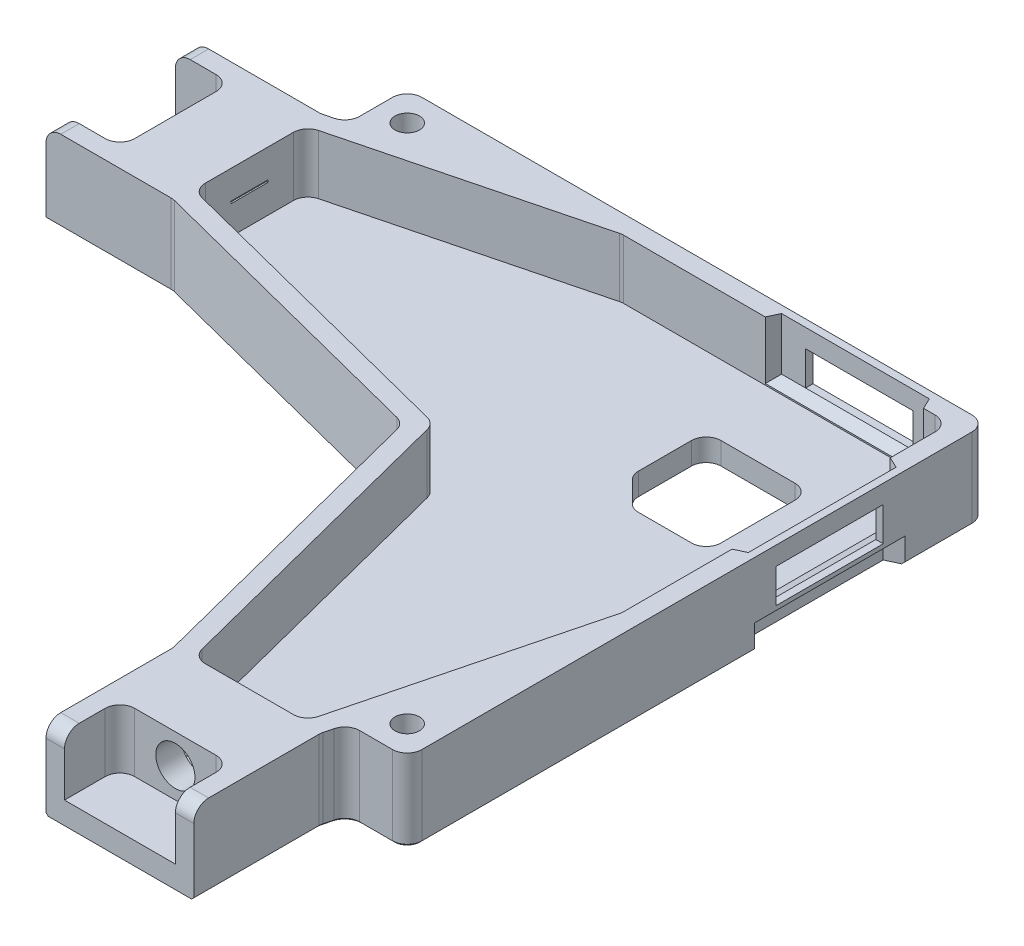
SolidWorks part; units mm, degrees
ref_plane "Front Plane" through (0, 0, 0) normal (0, 0, 1) x (1, 0, 0)
ref_plane "Top Plane" through (0, 0, 0) normal (0, 1, 0) x (1, 0, 0)
ref_plane "Right Plane" through (0, 0, 0) normal (1, 0, 0) x (0, 0, -1)
sketch "x Sensor" plane through (0, 0, 0) normal (0, 0, 1) x (1, 0, 0)
  line L0 (-13, 0) -> (0, 0) construction
  line L1 (-22.5, 1.5) -> (-13, 1.5)
  line L2 (-22.5, 1.5) -> (-22.5, -1.5)
  line L3 (-22.5, -1.5) -> (-13, -1.5)
  line L4 (-13, 1.5) -> (-13, -1.5)
  point P4 (-13, 0)
  dimension "D1" = 13
  dimension "D2" = 3
  dimension "D3" = 9.5
sketch "y Sensor" plane through (0, 0, 0) normal (1, 0, 0) x (0, 0, -1)
  line L0 (-13, 0) -> (0, 0) construction
  line L1 (-13, 1.5) -> (-22.5, 1.5)
  line L2 (-13, 1.5) -> (-13, -1.5)
  line L3 (-13, -1.5) -> (-22.5, -1.5)
  line L4 (-22.5, 1.5) -> (-22.5, -1.5)
  line L5 (0, 1.5) -> (0, -1.5) construction
  dimension "D1" = 9.5
  dimension "D2" = 13
ref_plane "y LED plane" through (-80, 0, 0) normal (1, 0, 0) x (0, 0, -1)
ref_plane "x LED plane" through (0, 0, 80) normal (0, 0, 1) x (1, 0, 0)
sketch "y LED" plane through (-80, 0, 0) normal (1, 0, 0) x (0, 0, -1)
  line L0 (-17.75, 1.5) -> (-17.75, -1.5) construction
  line L1 (-13, 1.5) -> (-22.5, 1.5) construction
  line L2 (-13, -1.5) -> (-22.5, -1.5) construction
  line L3 (-25.25, 0) -> (-10.25, 0) construction
  line L4 (-13, 0) -> (0, 0) construction
  point P10 (-17.75, 0)
  point P11 (-17.75, 0)
  dimension "D1" = 15
sketch "x LED" plane through (0, 0, 80) normal (0, 0, 1) x (1, 0, 0)
  line L0 (-17.75, 1.5) -> (-17.75, -1.5) construction
  line L1 (-22.5, 1.5) -> (-13, 1.5) construction
  line L2 (-22.5, -1.5) -> (-13, -1.5) construction
  line L3 (-25.25, 0) -> (-10.25, 0) construction
  point P9 (-17.75, 0)
  point P10 (-17.75, 0)
  dimension "D1" = 15
ref_plane "y LED cross-plane" through (0, 0, 17.75) normal (0, 0, 1) x (0, -1, 0)
ref_plane "x LED cross-plane" through (-17.75, 0, 0) normal (1, 0, 0) x (0, -1, 0)
ref_plane "Floor plane" through (0, -4, 0) normal (0, 1, 0) x (1, 0, 0)
ref_plane "Ceiling plane" through (0, 4, 0) normal (0, 1, 0) x (1, 0, 0)
sketch "Sketch10" plane through (0, -4, 0) normal (0, 1, 0) x (1, 0, 0)
  line L0 (0, 0) -> (-40, 0)
  line L1 (-40, 0) -> (-80, -10.25)
  line L2 (-80, -25.25) -> (-80, -10.25) construction
  line L3 (-80, -10.25) -> (-95, -10.25)
  line L4 (-95, -10.25) -> (-95, -25.25) construction
  line L5 (-95, -25.25) -> (-80, -25.25)
  line L6 (-80, -25.25) -> (-36.4179, -36.4179)
  line L7 (-40, -35.5) -> (-80, -25.25) construction
  line L8 (-36.4179, -36.4179) -> (-25.25, -80)
  line L9 (-25.25, -80) -> (-10.25, -80) construction
  line L10 (-25.25, -80) -> (-25.25, -95)
  line L11 (-25.25, -95) -> (-10.25, -95) construction
  line L12 (-10.25, -95) -> (-10.25, -80)
  line L13 (-10.25, -80) -> (0, -40)
  line L14 (0, -40) -> (0, 0)
  line L15 (-95, -17.75) -> (-51.5337, -17.75) construction
  line L16 (-17.75, -95) -> (-17.75, -69.9842) construction
  line L17 (-40.3152, 2.5) -> (-80.3152, -7.75)
  line L18 (-80.3152, -7.75) -> (-97.5, -7.75)
  line L19 (-97.5, -7.75) -> (-97.5, -10.25)
  line L20 (-97.5, -27.75) -> (-80.3152, -27.75)
  line L21 (-80.3152, -27.75) -> (-38.4723, -38.4723)
  line L23 (-38.4723, -38.4723) -> (-27.75, -80.3152)
  line L24 (-27.75, -80.3152) -> (-27.75, -97.5)
  line L25 (-27.75, -97.5) -> (-25.25, -97.5)
  line L26 (-7.75, -97.5) -> (-7.75, -80.3152)
  line L27 (-7.75, -80.3152) -> (2.5, -40.3152)
  line L28 (2.5, -40.3152) -> (2.5, 2.5)
  line L29 (2.5, 2.5) -> (-40.3152, 2.5)
  line L30 (-95, -10.25) -> (-97.5, -10.25)
  line L31 (-95, -25.25) -> (-97.5, -25.25)
  line L32 (-97.5, -10.25) -> (-97.5, -25.25) construction
  line L33 (-97.5, -7.75) -> (-97.5, -27.75) construction
  line L34 (-97.5, -25.25) -> (-97.5, -27.75)
  line L35 (-25.25, -95) -> (-25.25, -97.5)
  line L36 (-10.25, -95) -> (-10.25, -97.5)
  line L37 (-25.25, -97.5) -> (-10.25, -97.5) construction
  line L38 (-27.75, -97.5) -> (-7.75, -97.5) construction
  line L39 (-10.25, -97.5) -> (-7.75, -97.5)
  line L40 (-19.0553, -40.8671) -> (-36.4179, -36.4179) construction
  line L41 (-38.4723, -38.4723) -> (-38.4723, -38.4723) construction
  line L42 (-25.25, -80) -> (-35.5, -40) construction
  line L43 (-80.3152, -27.75) -> (-38.4723, -38.4723) construction
  line L44 (-80, -25.25) -> (-19.0553, -40.8671) construction
  dimension "D2" = 40
  dimension "D3" = 15
  dimension "D4" = 2.5
sketch "Max Shadows" plane through (0, 0, 0) normal (0, 1, 0) x (1, 0, 0)
  line L0 (-80, -17.75) -> (0, -13) construction
  line L1 (0, -13) -> (0, -22.5) construction
  line L2 (0, -22.5) -> (-80, -17.75) construction
  line L3 (0, -40) -> (0, 0) construction
  line L4 (-17.75, -80) -> (-22.5, 0) construction
  line L5 (-25.25, -80) -> (-10.25, -80) construction
  line L6 (-22.5, 0) -> (-13, 0) construction
  line L7 (0, 0) -> (-40, 0) construction
  line L8 (-17.75, -80) -> (-13, 0) construction
extrude "Boss-Extrude3" add sketch "Sketch10" along normal up to surface (8 mm away) up to plane "Ceiling plane"
sketch "Sketch12" plane through (0, -4, 0) normal (0, 1, 0) x (1, 0, 0)
  line L0 (-97.5, -10.25) -> (-97.5, -25.25) construction
  line L1 (-97.5, -7.75) -> (-97.5, -10.25) construction
  line L2 (-80.3152, -7.75) -> (-97.5, -7.75) construction
  line L3 (-40.3152, 2.5) -> (-80.3152, -7.75) construction
  line L4 (2.5, 2.5) -> (-40.3152, 2.5) construction
  line L5 (2.5, -40.3152) -> (2.5, 2.5) construction
  line L6 (-7.75, -80.3152) -> (2.5, -40.3152) construction
  line L7 (-7.75, -97.5) -> (-7.75, -80.3152) construction
  line L8 (-10.25, -97.5) -> (-7.75, -97.5) construction
  line L9 (-25.25, -97.5) -> (-10.25, -97.5) construction
  line L10 (-27.75, -97.5) -> (-25.25, -97.5) construction
  line L11 (-27.75, -80.3152) -> (-27.75, -97.5) construction
  line L12 (-38.4723, -38.4723) -> (-27.75, -80.3152) construction
  line L13 (-97.5, -25.25) -> (-97.5, -27.75) construction
  line L14 (-97.5, -27.75) -> (-80.3152, -27.75) construction
  line L15 (-80.3152, -27.75) -> (-38.4723, -38.4723) construction
  line L17 (-97.5, -10.25) -> (-97.5, -25.25)
  line L18 (-97.5, -7.75) -> (-97.5, -10.25)
  line L19 (-80.3152, -7.75) -> (-97.5, -7.75)
  line L20 (-40.3152, 2.5) -> (-80.3152, -7.75)
  line L21 (2.5, 2.5) -> (-40.3152, 2.5)
  line L22 (2.5, -40.3152) -> (2.5, 2.5)
  line L23 (-7.75, -80.3152) -> (2.5, -40.3152)
  line L24 (-7.75, -97.5) -> (-7.75, -80.3152)
  line L25 (-10.25, -97.5) -> (-7.75, -97.5)
  line L26 (-25.25, -97.5) -> (-10.25, -97.5)
  line L27 (-27.75, -97.5) -> (-25.25, -97.5)
  line L28 (-27.75, -80.3152) -> (-27.75, -97.5)
  line L29 (-38.4723, -38.4723) -> (-27.75, -80.3152)
  line L30 (-97.5, -25.25) -> (-97.5, -27.75)
  line L31 (-97.5, -27.75) -> (-80.3152, -27.75)
  line L32 (-80.3152, -27.75) -> (-38.4723, -38.4723)
extrude "Boss-Extrude4" add sketch "Sketch12" against normal blind 3
sketch "Sketch13" plane through (0, 0, 17.75) normal (0, 0, 1) x (0, -1, 0)
  line L0 (-4, -80) -> (-0.15, -80)
  line L1 (4, -80) -> (4, -84.05)
  line L2 (4, -97.5) -> (4, -80) construction
  line L3 (-4, -80) -> (4, -80) construction
  line L5 (0.15, -80) -> (4, -80)
  line L6 (-0.15, -80) -> (0.15, -80) construction
  line L8 (-0.15, -80) -> (-0.15, -80.2)
  line L9 (-4, -80) -> (-4, -90)
  line L10 (-4, -97.5) -> (-4, -80) construction
  line L11 (-4, -90) -> (4, -90)
  line L12 (4, -90) -> (4, -86.5)
  line L13 (4, -86.5) -> (-3, -86.5)
  line L14 (-3, -86.5) -> (-3, -83.05)
  line L15 (-0.15, -80.2) -> (-3, -83.05)
  line L16 (0, -80) -> (0, -86.5) construction
  line L17 (-2.5, -90) -> (-2.5, -86.5) construction
  line L18 (-2.5, -86.5) -> (-2.5, -85.2) construction
  line L19 (2.5, -90) -> (2.5, -86.5) construction
  line L20 (2.5, -86.5) -> (2.5, -85.2) construction
  line L21 (0.15, -80) -> (0.15, -80.2)
  line L22 (0.15, -80.2) -> (4, -84.05)
  arc A0 (-2.5, -85.2) -> (2.5, -85.2) centre (0, -85.2) cw construction
  point P13 (0, -80)
  point P26 (0, -82.7)
  dimension "D3" = 7.3
  dimension "D1" = 0.3
  dimension "D2" = 1
  dimension "D4" = 5
  dimension "D5" = 45
  dimension "D6" = 6.5
  dimension "D7" = 10
  dimension "D8" = 0.2
extrude "Boss-Extrude5" add sketch "Sketch13" along normal up to next and the other way up to next
sketch "Sketch14" plane through (-90, 0, 0) normal (-1, 0, 0) x (0, 0, 1)
  line L0 (17.75, 1.5) -> (17.75, -1.5) construction
  circle A0 centre (17.75, 0) radius 2.65
  dimension "D1" = 5.3
extrude "Cut-Extrude1" cut sketch "Sketch14" against normal up to next
sketch "Sketch38" [suppressed] plane through (-140, 0, 0) normal (-1, 0, 0) x (0, 0, 1)
  line L0 (17.75, 2.5) -> (17.75, -2.5) construction
  line L1 (16.45, 2.5) -> (19.05, 2.5)
  line L2 (16.45, 2.5) -> (16.45, -2.5)
  line L3 (16.45, -2.5) -> (19.05, -2.5)
  line L4 (19.05, 2.5) -> (19.05, -2.5)
  point P6 (17.75, 0)
  dimension "D1" = 5
  dimension "D2" = 2.6
extrude "Cut-Extrude20" [suppressed] cut sketch "Sketch38" against normal blind 2.3
sketch "Sketch15" plane through (-17.75, 0, 0) normal (1, 0, 0) x (0, -1, 0)
  line L0 (-4, -80) -> (-0.15, -80)
  line L1 (4, -80) -> (4, -84.05)
  line L5 (0.15, -80) -> (4, -80)
  line L6 (-0.15, -80) -> (0.15, -80) construction
  line L8 (-0.15, -80) -> (-0.15, -80.2)
  line L9 (-4, -80) -> (-4, -90)
  line L11 (-4, -90) -> (4, -90)
  line L12 (4, -90) -> (4, -86.5)
  line L13 (4, -86.5) -> (-3, -86.5)
  line L14 (-3, -86.5) -> (-3, -83.05)
  line L15 (-0.15, -80.2) -> (-3, -83.05)
  line L16 (0, -80) -> (0, -86.5) construction
  line L17 (-2.5, -90) -> (-2.5, -86.5) construction
  line L18 (-2.5, -86.5) -> (-2.5, -85.2) construction
  line L19 (2.5, -90) -> (2.5, -86.5) construction
  line L20 (2.5, -86.5) -> (2.5, -85.2) construction
  line L21 (0.15, -80) -> (0.15, -80.2)
  line L22 (0.15, -80.2) -> (4, -84.05)
  arc A0 (-2.5, -85.2) -> (2.5, -85.2) centre (0, -85.2) cw construction
extrude "Boss-Extrude6" add sketch "Sketch15" along normal up to next and the other way up to next
sketch "Sketch16" plane through (0, 0, 90) normal (0, 0, -1) x (-1, 0, 0)
  circle A0 centre (17.75, 0) radius 2.65
extrude "Cut-Extrude2" cut sketch "Sketch16" along normal up to next
sketch "Sketch39" [suppressed] plane through (0, 0, 140) normal (0, 0, 1) x (1, 0, 0)
  line L1 (-16.45, 2.5) -> (-19.05, 2.5)
  line L2 (-16.45, 2.5) -> (-16.45, -2.5)
  line L3 (-16.45, -2.5) -> (-19.05, -2.5)
  line L4 (-19.05, 2.5) -> (-19.05, -2.5)
  line L5 (-16.45, 2.5) -> (-19.05, -2.5) construction
  line L6 (-16.45, -2.5) -> (-19.05, 2.5) construction
  point P0 (-17.75, 0)
  dimension "D1" = 2.6
  dimension "D2" = 5
extrude "Cut-Extrude21" [suppressed] cut sketch "Sketch39" against normal blind 2.3
sketch "Sketch18" plane through (0, 0, -2.5) normal (0, 0, -1) x (-1, 0, 0)
  line L0 (-2.5, -7) -> (40.3152, -7) construction
  line L1 (-2.5, 4) -> (80.3152, 4)
  line L2 (-2.5, 4) -> (-2.5, -7)
  line L3 (-2.5, -7) -> (80.3152, -7)
  line L4 (80.3152, 4) -> (80.3152, -7)
  line L6 (80.3152, 4) -> (80.3152, -7) construction
extrude "Cut-Extrude4" cut sketch "Sketch18" against normal offset from surface (1.5 mm away) 1 up to face at (-20, 0, 0)
sketch "Sketch20" plane through (2.5, 0, 0) normal (1, 0, 0) x (0, 0, -1)
  line L0 (-40.3152, 4) -> (1, 4) construction
  line L1 (1, -7) -> (-80.3152, -7)
  line L2 (1, -7) -> (1, 4)
  line L3 (1, 4) -> (-80.3152, 4)
  line L4 (-80.3152, -7) -> (-80.3152, 4)
  line L5 (-80.3152, 4) -> (-80.3152, -7) construction
extrude "Cut-Extrude6" cut sketch "Sketch20" against normal offset from surface (1.5 mm away) 1 contours L1 L4 L3 L2 up to face at (0, 0, 20)
sketch "Sketch21" plane through (0, 0, 0) normal (0, 0, 1) x (1, 0, 0)
  line L0 (-40, -4) -> (-50.0713, -4)
  line L1 (-50.0713, -4) -> (-50.0713, 4)
  line L2 (-50.0713, 4) -> (-40, 4)
  line L3 (-46.1689, 4) -> (-80.3152, 4) construction
  line L4 (0, 4) -> (-40, 4)
  line L6 (-40, -4) -> (0, -4)
  line L7 (0, -4) -> (0, 4)
  line L8 (0, 4) -> (-40, 4)
  line L10 (-40, -4) -> (0, -4)
  line L11 (0, -4) -> (0, 4)
  line L14 (-40, 4) -> (-40, -4)
  dimension "D1" = 0
extrude "Boss-Extrude7" add sketch "Sketch21" along normal offset from surface (1.5 mm away) 2.5 up to face at (-22.5844, -1.5, -1)
sketch "Sketch22" plane through (0, 0, 0) normal (-1, 0, 0) x (0, 0, 1)
  line L0 (40, -4) -> (50.0713, -4)
  line L1 (50.0713, -4) -> (50.0713, 4)
  line L2 (50.0713, 4) -> (40, 4)
  line L4 (40, -4) -> (40, 4)
  line L5 (1.5, -4) -> (40, -4)
  line L7 (40, 4) -> (1.5, 4)
  line L8 (1.5, 4) -> (1.5, -4)
  line L9 (1.5, -4) -> (40, -4)
  line L11 (40, 4) -> (1.5, 4)
  line L13 (1.5, 4) -> (1.5, -4)
  dimension "D1" = 0
extrude "Boss-Extrude8" add sketch "Sketch22" along normal offset from surface (1.5 mm away) 2.5 up to face at (1, -1.5, 22.5844)
sketch "Sketch17" plane through (0, 0, 0) normal (0, 0, 1) x (1, 0, 0)
  line L1 (-8, -3.1) -> (-22.5, -3.1)
  line L2 (-8, -3.1) -> (-8, 1.5)
  line L3 (-8, 1.5) -> (-22.5, 1.5)
  line L4 (-22.5, -3.1) -> (-22.5, 1.5)
  dimension "D1" = 14.5
  dimension "D2" = 4.6
extrude "Cut-Extrude3" cut sketch "Sketch17" against normal through all and the other way up to next
sketch "Sketch19" plane through (0, 0, 0) normal (1, 0, 0) x (0, 0, -1)
  line L1 (-13, -3.1) -> (-27.5, -3.1)
  line L2 (-13, -3.1) -> (-13, 1.5)
  line L3 (-13, 1.5) -> (-27.5, 1.5)
  line L4 (-27.5, -3.1) -> (-27.5, 1.5)
  dimension "D1" = 14.5
  dimension "D2" = 4.6
extrude "Cut-Extrude5" cut sketch "Sketch19" along normal through all and the other way up to next
sketch "Sketch23" plane through (-1.5, 0, 0) normal (-1, 0, 0) x (0, 0, 1)
  line L0 (27.5, -3.1) -> (13, -3.1) construction
  line L1 (10.25, 1.5) -> (30.25, 1.5)
  line L2 (10.25, 1.5) -> (10.25, -3.1)
  line L3 (10.25, -3.1) -> (30.25, -3.1)
  line L4 (30.25, 1.5) -> (30.25, -3.1)
  point P4 (20.25, -3.1)
  point P7 (20.25, -3.1)
  dimension "D1" = 20
extrude "Cut-Extrude7" cut sketch "Sketch23" against normal up to surface (1.5 mm away) up to plane "Right Plane"
sketch "Sketch25" plane through (-36, 0, 1.5) normal (0, 0, 1) x (1, 0, 0)
  line L1 (10.25, 1.5) -> (30.25, 1.5)
  line L2 (10.25, 1.5) -> (10.25, -3.1)
  line L3 (10.25, -3.1) -> (30.25, -3.1)
  line L4 (30.25, 1.5) -> (30.25, -3.1)
extrude "Cut-Extrude9" cut sketch "Sketch25" against normal up to surface (1.5 mm away) up to plane "Front Plane"
chamfer "Chamfer2" distance 1.5 angle 25 6 edges at (-1.5, -3.1, 20.25) (-1.5, -0.8, 30.25) (-1.5, -0.8, 10.25) (-5.75, -0.8, 1.5) (-25.75, -0.8, 1.5) (-15.75, -3.1, 1.5) first distance on face at (-0.125, -3.1, 20.25) first distance on face at (-0.75, -0.8, 30.25) first distance on face at (-0.75, -0.8, 10.25) first distance on face at (-5.75, -0.8, 0.75) first distance on face at (-25.75, -0.8, 0.75) first distance on face at (-15.5, -3.1, 0.125)
sketch "Sketch28" plane through (0, 0, -1) normal (0, 0, -1) x (-1, 0, 0)
  line L0 (-1, -7) -> (46.1689, -7) construction
  line L1 (24.5, -4.6) -> (6, -4.6)
  line L2 (24.5, -4.6) -> (24.5, -7)
  line L3 (24.5, -7) -> (6, -7)
  line L4 (6, -4.6) -> (6, -7)
  line L7 (22.5, -3.1) -> (8, -3.1) construction
  line L8 (8, -3.1) -> (8, 1.5) construction
  line L10 (22.5, 1.5) -> (22.5, -3.1) construction
  dimension "D1" = 1.5
  dimension "D2" = 2
  dimension "D3" = 2
extrude "Cut-Extrude10" cut sketch "Sketch28" against normal blind 2
sketch "Sketch29" plane through (1, 0, 5) normal (-1, 0, 0) x (0, 0, 1)
  line L0 (22.5, -3.1) -> (8, -3.1) construction
  line L1 (24.5, -4.6) -> (6, -4.6)
  line L2 (24.5, -4.6) -> (24.5, -7)
  line L3 (24.5, -7) -> (6, -7)
  line L4 (6, -4.6) -> (6, -7)
  line L5 (22.5, 1.5) -> (22.5, -3.1) construction
  line L6 (8, -3.1) -> (8, 1.5) construction
  line L7 (41.1689, -7) -> (-6, -7) construction
  dimension "D1" = 1.5
  dimension "D2" = 2
  dimension "D3" = 2
extrude "Cut-Extrude11" cut sketch "Sketch29" along normal blind 2
chamfer "Chamfer3" distance 2 angle 25 6 edges at (-24.5, -5.8, -1) (-15.25, -4.6, -1) (-6, -5.8, -1) (1, -5.8, 11) (1, -5.8, 29.5) (1, -4.6, 20.25) first distance on face at (-24.5, -5.8, 0) first distance on face at (-15.25, -4.6, 0) first distance on face at (-6, -5.8, 0) first distance on face at (0, -5.8, 11) first distance on face at (0, -5.8, 29.5) first distance on face at (0, -4.6, 20.25)
sketch "Sketch30" plane through (0, -4, 0) normal (0, 1, 0) x (1, 0, 0)
  line L0 (-13.8206, -13.8206) -> (-21.2389, -21.2389) construction
  line L1 (-14.2856, -21.6518) -> (-21.6518, -14.2856) construction
  line L2 (-80, -17.75) -> (0, -13) construction
  line L3 (-17.75, -80) -> (-22.5, 0) construction
  line L4 (0, -22.5) -> (-80, -17.75) construction
  line L5 (-17.75, -80) -> (-13, 0) construction
  line L7 (-10.9687, -10.9687) -> (-24.9687, -10.9687)
  line L8 (-10.9687, -10.9687) -> (-10.9687, -24.9687)
  line L9 (-10.9687, -24.9687) -> (-24.9687, -24.9687)
  line L10 (-24.9687, -10.9687) -> (-24.9687, -24.9687)
  line L11 (-10.9687, -10.9687) -> (-24.9687, -24.9687) construction
  line L12 (-10.9687, -24.9687) -> (-24.9687, -10.9687) construction
  point P12 (-17.9687, -17.9687)
  point P13 (-17.9687, -17.9687)
  dimension "D1" = 14
extrude "Cut-Extrude12" cut sketch "Sketch30" against normal through all
fillet "Fillet1" radius 2 3 edges at (-10.9687, -5.5, 10.9687) (-10.9687, -5.5, 24.9687) (-24.9687, -5.5, 10.9687)
sketch "Sketch31" plane through (0, -0.15, 0) normal (0, 1, 0) x (1, 0, 0)
  line L0 (-80.2, -10.25) -> (-80.2, -25.25) construction
  line L1 (-80, -10.25) -> (-80.2, -10.25)
  line L2 (-80, -10.25) -> (-80, -15.25)
  line L3 (-80, -15.25) -> (-80.2, -15.25)
  line L4 (-80.2, -10.25) -> (-80.2, -15.25)
  line L6 (-80, -25.25) -> (-80.2, -25.25)
  line L7 (-80, -25.25) -> (-80, -20.25)
  line L8 (-80, -20.25) -> (-80.2, -20.25)
  line L9 (-80.2, -25.25) -> (-80.2, -20.25)
  dimension "D1" = 5
extrude "Boss-Extrude9" add sketch "Sketch31" along normal up to next
sketch "Sketch32" plane through (0, -0.15, 0) normal (0, 1, 0) x (1, 0, 0)
  line L0 (-25.25, -80.2) -> (-10.25, -80.2) construction
  line L1 (-25.25, -80) -> (-20.25, -80)
  line L2 (-25.25, -80) -> (-25.25, -80.2)
  line L3 (-25.25, -80.2) -> (-20.25, -80.2)
  line L4 (-20.25, -80) -> (-20.25, -80.2)
  line L6 (-10.25, -80) -> (-15.25, -80)
  line L7 (-10.25, -80) -> (-10.25, -80.2)
  line L8 (-10.25, -80.2) -> (-15.25, -80.2)
  line L9 (-15.25, -80) -> (-15.25, -80.2)
  dimension "D1" = 5
extrude "Boss-Extrude10" add sketch "Sketch32" along normal up to next
sketch "Sketch33" plane through (0, -7, 0) normal (0, -1, 0) x (1, 0, 0)
  line L0 (1, -1) -> (-38.4723, 38.4723) construction
  line L2 (-46.1689, -1) -> (-80.3152, 7.75) construction
  line L3 (-46.1689, -1) -> (-77.3884, -1)
  line L4 (-46.1689, -1) -> (-77.3884, 7)
  line L5 (1, 77.3884) -> (-7, 77.3884)
  line L6 (-77.3884, -1) -> (-77.3884, 7)
  line L7 (1, 46.1689) -> (-7, 77.3884)
  line L8 (1, 46.1689) -> (1, 77.3884)
  dimension "D1" = 8
extrude "Boss-Extrude11" add sketch "Sketch33" against normal up to surface (11 mm away) up to face at (-47.7636, 4, 47.7636)
sketch "Sketch35" plane through (0, 4, 0) normal (0, 1, 0) x (1, 0, 0)
  line L0 (1, 1) -> (-54.474, -54.474) construction
  line L2 (-77.3884, -7) -> (-77.3884, 1) construction
  line L3 (1, 1) -> (-77.3884, 1) construction
  circle A0 centre (-73.3884, -3) radius 1.65
  circle A1 centre (-3, -73.3884) radius 1.65
  dimension "D1" = 4
  dimension "D3" = 3.3
  dimension "D2" = 4
  dimension "D4" = 45
extrude "Cut-Extrude13" cut sketch "Sketch35" against normal through all
fillet "Fillet2" radius 2 26 edges at (-90, 0, 10.25) (-90, 0, 25.25) (-25.25, 0, 90) (-10.25, 0, 90) (-97.5, 4, 9) (-97.5, 4, 26.5) (-80.3152, -1.5, 7.75) (1, -1.5, -1) (-7.75, -1.5, 80.3152) (-27.75, -1.5, 80.3152) (-80.3152, -1.5, 27.75) (-1.5, 0, 45.8537) (-1.5, 0, 1.5) (-45.8537, 0, 1.5) (-80, 0, 10.25) (-80, 0, 25.25) (-10.25, 0, 80) (-25.25, 0, 80) (-77.3884, -1.5, -1) (-77.3884, -1.5, 7) (1, -1.5, 77.3884) (-7, -1.5, 77.3884) (-9, 4, 97.5) (-26.5, 4, 97.5) (-36.4179, 0, 36.4179) (-38.4723, -1.5, 38.4723)
chamfer "Chamfer4" distance 0.3 angle 45 24 edges at (-50.4105, -7, -1) (-76.8026, -7, -0.4142) (-77.3884, -7, 3.2239) (-77.8084, -7, 6.6741) (-79.4814, -7, 7.5363) (-80.3172, -7, 7.7343) (-89.0337, -7, 7.75) (-3.0337, -7, -1) (0.4142, -7, -0.4142) (1, -7, 5.5337) (1, -7, 52.9105) (0.4142, -7, 76.8026) (-3.2239, -7, 77.3884) (-6.6741, -7, 77.8084) (-7.5363, -7, 79.4814) (-7.7343, -7, 80.3172) (-7.75, -7, 89.0337) (-27.75, -7, 89.0337) (-27.7657, -7, 80.3172) (-32.9955, -7, 59.8451) (-59.8451, -7, 32.9955) (-80.3172, -7, 27.7657) (-89.0337, -7, 27.75) (-38.7015, -7, 38.7015)
chamfer "Chamfer5" distance 4 angle 45 1 edges at (-24.9687, -5.5, 24.9687)
fillet "Fillet3" radius 2 2 edges at (-20.9687, -5.5, 24.9687) (-24.9687, -5.5, 20.9687)
sketch "Sketch37" plane through (0, 1.5, 0) normal (0, -1, 0) x (1, 0, 0)
  line L0 (1, 27.5) -> (0, 27.5) construction
  line L1 (0, 27.5) -> (0, 30.25) construction
  line L2 (0, 30.25) -> (-1.5, 30.9495) construction
  line L3 (-1.5, 30.9495) -> (-1.5, 9.5505) construction
  line L4 (-1.5, 9.5505) -> (0, 10.25) construction
  line L5 (0, 10.25) -> (0, 13) construction
  line L6 (0, 13) -> (1, 13) construction
  line L7 (1, 13) -> (1, 27.5) construction
  line L8 (-25.75, 0) -> (-22.5, 0) construction
  line L9 (-22.5, 0) -> (-22.5, -1) construction
  line L10 (-22.5, -1) -> (-8, -1) construction
  line L11 (-8, -1) -> (-8, 0) construction
  line L12 (-8, 0) -> (-5.75, 0) construction
  line L13 (-5.75, 0) -> (-5.0505, 1.5) construction
  line L14 (-5.0505, 1.5) -> (-26.4495, 1.5) construction
  line L15 (-26.4495, 1.5) -> (-25.75, 0) construction
  line L16 (1, 27.5) -> (0, 27.5) construction
  line L17 (0, 27.5) -> (0, 30.25)
  line L18 (0, 30.25) -> (-1.5, 30.9495)
  line L19 (-1.5, 30.9495) -> (-1.5, 9.5505)
  line L20 (-1.5, 9.5505) -> (0, 10.25)
  line L21 (0, 10.25) -> (0, 13)
  line L22 (0, 13) -> (1, 13) construction
  line L23 (1, 13) -> (1, 27.5) construction
  line L24 (-25.75, 0) -> (-22.5, 0)
  line L25 (-22.5, 0) -> (-22.5, -1) construction
  line L26 (-22.5, -1) -> (-8, -1) construction
  line L27 (-8, -1) -> (-8, 0) construction
  line L28 (-8, 0) -> (-5.75, 0)
  line L29 (-5.75, 0) -> (-5.0505, 1.5)
  line L30 (-5.0505, 1.5) -> (-26.4495, 1.5)
  line L31 (-26.4495, 1.5) -> (-25.75, 0)
  line L32 (-22.5, 0) -> (-8, 0)
  line L33 (0, 13) -> (0, 27.5)
extrude "Cut-Extrude14" cut sketch "Sketch37" against normal through all
sketch "Sketch44" [suppressed] plane through (0, -4, 0) normal (0, 1, 0) x (1, 0, 0)
  line L0 (-114.2009, -8.7778) -> (-114.2009, -26.7222)
  line L1 (-130, -10.25) -> (-36.0976, -1.5) construction
  line L2 (-34.1788, -34.1788) -> (-130, -25.25) construction
  line L3 (-114.2009, -26.7222) -> (-130, -25.25)
  line L4 (-130, -25.25) -> (-142.5, -25.25)
  line L5 (-142.5, -25.25) -> (-142.5, -10.25)
  line L6 (-142.5, -10.25) -> (-130, -10.25)
  line L7 (-130, -10.25) -> (-114.2009, -8.7778)
  line L9 (-116.7016, -6.5) -> (-116.7016, -26.4892) construction
  line L10 (-116.7016, -12.9955) -> (-114.2009, -12.9955) construction
  line L11 (-136.3081, -7.75) -> (-136.25, -10.25) construction
  line L12 (-130.1162, -7.75) -> (-142.5, -7.75) construction
extrude "Boss-Extrude14" [suppressed] add sketch "Sketch44" along normal up to surface (8 mm away) up to face at (-26.1451, 4, 26.8951)
sketch "Sketch46" [suppressed] plane through (-142.5, 0, 0) normal (-1, 0, 0) x (0, 0, 1)
  line L0 (17.75, 0) -> (17.75, 9.8019) construction
  line L2 (7.75, 4) -> (27.75, 4) construction
  line L3 (9.6877, 4) -> (25.8123, 4)
  arc A0 (25.8123, 4) -> (9.6877, 4) centre (17.75, 0) ccw
  point P8 (17.75, 4)
  dimension "D1" = 9
extrude "Boss-Extrude15" [suppressed] add sketch "Sketch46" against normal offset from surface (24.7984 mm away) 1 up to face at (-77.3884, -1.35, 3.2239)
sketch "Sketch41" [suppressed] plane through (-130, 0, 0) normal (1, 0, 0) x (0, 0, -1)
  circle A0 centre (-17.75, 0) radius 6.2
  dimension "D1" = 12.4
extrude "Cut-Extrude22" [suppressed] cut sketch "Sketch41" against normal through all and the other way blind 8.18
sketch "Sketch47" [suppressed] plane through (-130, 0, 0) normal (1, 0, 0) x (0, 0, -1)
  circle A0 centre (-17.75, 0) radius 1.5
  dimension "D1" = 3
extrude "Cut-Extrude24" [suppressed] cut sketch "Sketch47" along normal up to surface (15.7991 mm away)
sketch "Sketch48" [suppressed] plane through (0, -4, 0) normal (0, 1, 0) x (1, 0, 0)
  line L0 (-25.25, -142.5) -> (-10.25, -142.5)
  line L1 (-10.25, -142.5) -> (-10.25, -130)
  line L2 (-10.25, -130) -> (-8.7778, -114.2009)
  line L3 (-1.5, -36.0976) -> (-10.25, -130) construction
  line L4 (-8.7778, -114.2009) -> (-26.7222, -114.2009)
  line L5 (-25.25, -130) -> (-34.1788, -34.1788) construction
  line L6 (-26.7222, -114.2009) -> (-25.25, -130)
  line L7 (-25.25, -130) -> (-25.25, -142.5)
  line L8 (-11.5803, -114.2009) -> (-11.5803, -116.7016) construction
  line L9 (-10.25, -136.25) -> (-7.75, -136.3081) construction
  line L10 (-7.75, -142.5) -> (-7.75, -130.1162) construction
  line L11 (1, -116.7016) -> (-6.5, -116.7016) construction
extrude "Boss-Extrude16" [suppressed] add sketch "Sketch48" along normal up to surface (8 mm away) up to face at (-26.1451, 4, 26.8951)
sketch "Sketch49" [suppressed] plane through (0, 0, 142.5) normal (0, 0, 1) x (1, 0, 0)
  line L0 (-27.75, 4) -> (-7.75, 4) construction
  line L1 (-17.75, 7.9098) -> (-17.75, 4) construction
  line L2 (-25.8123, 4) -> (-9.6877, 4)
  arc A0 (-25.8123, 4) -> (-9.6877, 4) centre (-17.75, 0) cw
  dimension "D1" = 9
extrude "Boss-Extrude17" [suppressed] add sketch "Sketch49" against normal offset from surface (24.7984 mm away) 1 up to face at (-3.2239, -1.35, 77.3884)
sketch "Sketch51" [suppressed] plane through (0, 0, 130) normal (0, 0, 1) x (1, 0, 0)
  circle A0 centre (-17.75, 0) radius 6.2
  dimension "D1" = 12.4
extrude "Cut-Extrude25" [suppressed] cut sketch "Sketch51" along normal through all and the other way blind 8.18
sketch "Sketch52" [suppressed] plane through (0, 0, 130) normal (0, 0, 1) x (1, 0, 0)
  circle A0 centre (-17.75, 0) radius 1.5
  dimension "D1" = 3
extrude "Cut-Extrude26" [suppressed] cut sketch "Sketch52" against normal up to surface (15.7991 mm away)
equation "\"D1@Sketch39\"=\"D2@Sketch38\""
equation "\"D2@Sketch39\"=\"D1@Sketch38\""
equation "\"D1@Cut-Extrude21\"=\"D1@Cut-Extrude20\""
equation "\"D1@Sketch51\"=\"D1@Sketch41\""
equation "\"D2@Cut-Extrude25\"=\"D2@Cut-Extrude22\""
equation "\"D1@Sketch52\"=\"D1@Sketch47\""
